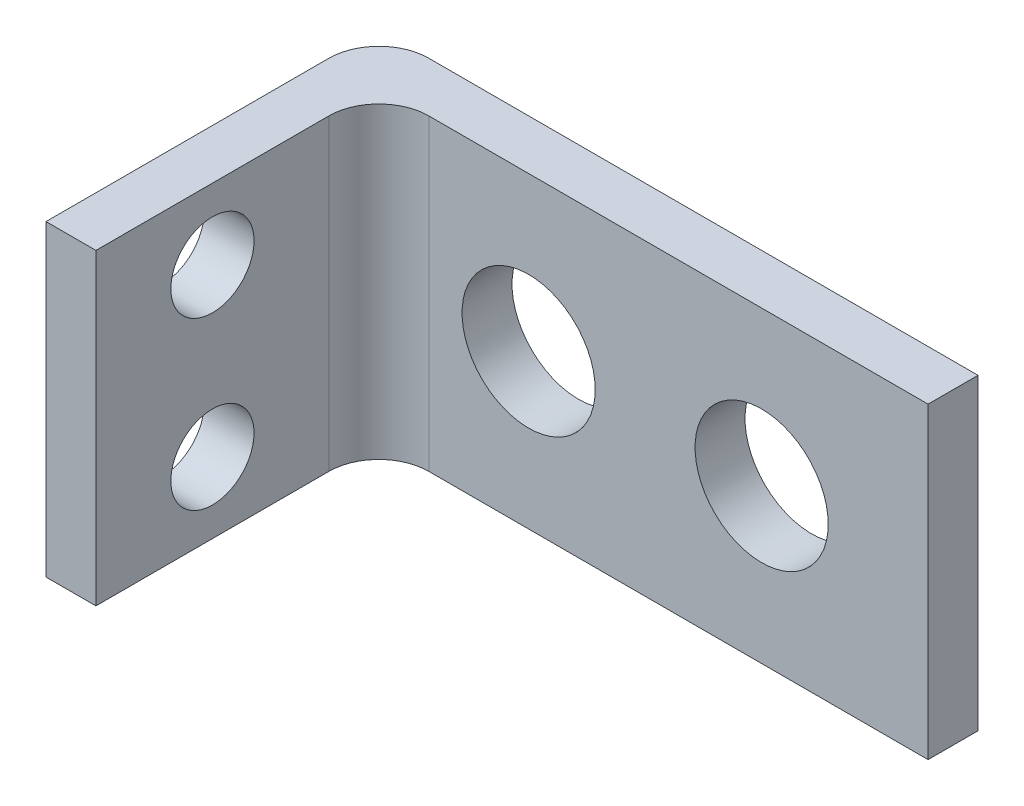
SolidWorks part; units mm, degrees
ref_plane "Front Plane" through (0, 0, 0) normal (0, 0, 1) x (1, 0, 0)
ref_plane "Top Plane" through (0, 0, 0) normal (0, 1, 0) x (1, 0, 0)
ref_plane "Right Plane" through (0, 0, 0) normal (1, 0, 0) x (0, 0, -1)
sketch "Sketch1" plane through (0, 0, 0) normal (0, 0, 1) x (1, 0, 0)
  line L0 (-19, 0) -> (19, 0) construction
  line L1 (-19, 9.25) -> (19, 9.25)
  line L2 (-19, 9.25) -> (-19, -9.25) construction
  line L3 (-19, -9.25) -> (19, -9.25)
  line L4 (19, 9.25) -> (19, -9.25)
  line L5 (-19, 9.25) -> (19, -9.25) construction
  line L6 (-19, -9.25) -> (19, 9.25) construction
  line L7 (-14, 9.25) -> (-14, -9.25)
  line L8 (-17, 9.25) -> (-17, -9.25)
  circle A0 centre (9, 0) radius 4
  circle A1 centre (-5, 0) radius 4
  point P0 (0, 0)
  dimension "D3" = 8
  dimension "D4" = 8
  dimension "D5" = 14
  dimension "D6" = 10
  dimension "D1" = 18.5
  dimension "D2" = 38
  dimension "D7" = 9
  dimension "D8" = 3
extrude "Boss-Extrude1" add sketch "Sketch1" along normal blind 3 contours L1 L7 L3 L4 A1 A0 | L1 L8 L3 L7 region at (-15.5, 0, 0) region at (2.5986, 0, 0)
extrude "Boss-Extrude2" add sketch "Sketch1<3>" along normal blind 20 contours L1 L8 L3 L7 region at (-15.5, 0, 0)
sketch "Sketch1<3>" plane through (0, 0, 0) normal (0, 0, 1) x (1, 0, 0) same geometry as "Sketch1"
fillet "Fillet1" radius 3 2 edges at (-17, 0, 0) (-14, 0, 3)
sketch "Sketch2" plane through (-14, 0, 0) normal (1, 0, 0) x (0, 0, -1)
  line L0 (-7.883, 0) -> (-96.7592, 0) construction
  line L1 (-102.8314, 39.815) -> (-6.2954, 39.815)
  line L2 (-102.8314, 39.815) -> (-102.8314, -39.815)
  line L3 (-102.8314, -39.815) -> (-6.2954, -39.815)
  line L4 (-6.2954, 39.815) -> (-6.2954, -39.815)
  line L5 (-102.8314, 39.815) -> (-6.2954, -39.815) construction
  line L6 (-102.8314, -39.815) -> (-6.2954, 39.815) construction
  line L7 (-40, 23.815) -> (-40, -23.815) construction
  line L8 (-3, 9.25) -> (-3, -9.25) construction
  line L9 (-56, 39.815) -> (-56, -39.815)
  line L10 (-40, -39.815) -> (-6, -9.25)
  line L11 (-40, 39.815) -> (-6, 9.25)
  circle A0 centre (-40, 23.815) radius 5.35
  circle A1 centre (-40, -23.815) radius 5.35
  circle A4 centre (-13, 5) radius 2.5
  circle A5 centre (-13, -5) radius 2.5
  point P0 (-54.5634, 0)
  point P11 (-40, 0)
  point P18 (-56, 0)
  dimension "D2" = 10.7
  dimension "D3" = 10.7
  dimension "D7" = 5
  dimension "D8" = 5
  dimension "D9" = 5
  dimension "D10" = 5
  dimension "D11" = 10
  dimension "D12" = 10
  dimension "D1" = 47.63
  dimension "D4" = 37
  dimension "D5" = 16
  dimension "D6" = 16
extrude "Cut-Extrude1" cut sketch "Sketch2" against normal through all contours A4 | A5 region at (-14, 5, 13) region at (-14, -5, 13)
